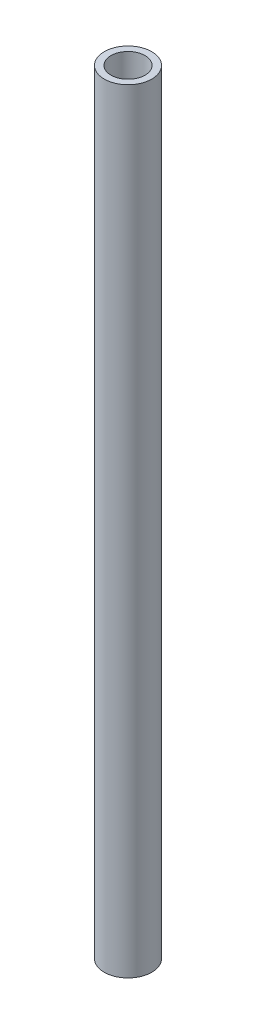
SolidWorks part; units mm, degrees
note: '?' marks a value the reader was unsure of.
material "Plain Carbon Steel"
ref_plane "Front Plane" through (0, 0, 0) normal (0, 0, 1) x (1, 0, 0)
ref_plane "Top Plane" through (0, 0, 0) normal (0, 1, 0) x (1, 0, 0)
ref_plane "Right Plane" through (0, 0, 0) normal (1, 0, 0) x (0, 0, -1)
sketch "Sketch1" plane through (0, 0, 0) normal (0, 1, 0) x (1, 0, 0)
  circle A0 centre (0, 0) radius 12.5
  circle A1 centre (0, 0) radius 17.5
  dimension "D1" = 25
  dimension "D2" = 35
extrude "Boss-Extrude1" add sketch "Sketch1" along normal mid plane 560
ref_plane "Plane sets base of Plate surface - Don't move :)" through (0, -160, 0) normal (0, -1, 0) x (-1, 0, 0)
sketch "Sketch5" plane through (0, 0, 0) normal (1, 0, 0) x (0, 0, -1)
  line L1 (12.407, 241.5319) -> (-12.593, 241.5319)
  line L2 (12.407, 241.5319) -> (12.407, 201.5319)
  line L3 (12.407, 201.5319) -> (-12.593, 201.5319)
  line L4 (-12.593, 241.5319) -> (-12.593, 201.5319)
  dimension "D1" = 40
  dimension "D2" = 25
ref_axis "Axis1" through (0, 280, 0) along (0, -1, 0)?
sketch "Sketch8" plane through (0, -280, 0) normal (0, -1, 0) x (1, 0, 0)
  circle A1 centre (0, 0) radius 17.5
  circle A2 centre (0, 0) radius 17.5
  dimension "D1" = 0
extrude "Boss-Extrude3" add sketch "Sketch8" along normal blind 10
extrude "Cut-Extrude2" cut sketch "Sketch9" against normal blind 899.5
sketch "Sketch9" plane through (-32.3028, 416.2892, -45.2219) normal (0, 1, 0) x (-0.9769, 0, 0.2137)
  circle A0 centre (-21.8901, 51.0814) radius 12.55
extrude "Cut-Extrude3" [suppressed] cut sketch "Sketch10" against normal blind 5
sketch "Sketch10" plane through (-25.1589, 226, 55.5571) normal (0, -1, 0) x (0.9695, 0, -0.2452)
  line L5 (60.7638, -17.1919) -> (15.2638, -17.1919)
  line L21 (8.2638, -37.1919) -> (13.2638, -37.1919)
  line L23 (62.7638, -27.1919) -> (62.7638, -19.1919)
  line L25 (62.7638, -76.1919) -> (62.7638, -68.1919)
  line L28 (13.2638, -37.1919) -> (13.2638, -58.1919)
  line L33 (13.2638, -58.1919) -> (8.2638, -58.1919)
  line L37 (8.2638, -58.1919) -> (8.2638, -68.1919)
  line L50 (15.2638, -78.1919) -> (60.7638, -78.1919)
  line L59 (8.2638, -68.1919) -> (13.2638, -68.1919)
  line L61 (13.2638, -68.1919) -> (13.2638, -76.1919)
  line L63 (62.7638, -68.1919) -> (67.7638, -68.1919)
  line L65 (67.7638, -68.1919) -> (67.7638, -58.1919)
  line L67 (67.7638, -58.1919) -> (62.7638, -58.1919)
  line L69 (62.7638, -58.1919) -> (62.7638, -37.1919)
  line L71 (62.7638, -37.1919) -> (67.7638, -37.1919)
  line L73 (67.7638, -37.1919) -> (67.7638, -27.1919)
  line L75 (67.7638, -27.1919) -> (62.7638, -27.1919)
  line L77 (13.2638, -19.1919) -> (13.2638, -27.1919)
  line L79 (13.2638, -27.1919) -> (8.2638, -27.1919)
  line L81 (8.2638, -27.1919) -> (8.2638, -37.1919)
  arc A5 (13.2638, -76.1919) -> (15.2638, -78.1919) centre (15.2638, -76.1919) ccw
  arc A7 (60.7638, -78.1919) -> (62.7638, -76.1919) centre (60.7638, -76.1919) ccw
  arc A29 (15.2638, -17.1919) -> (13.2638, -19.1919) centre (15.2638, -19.1919) ccw
  arc A35 (62.7638, -19.1919) -> (60.7638, -17.1919) centre (60.7638, -19.1919) ccw
